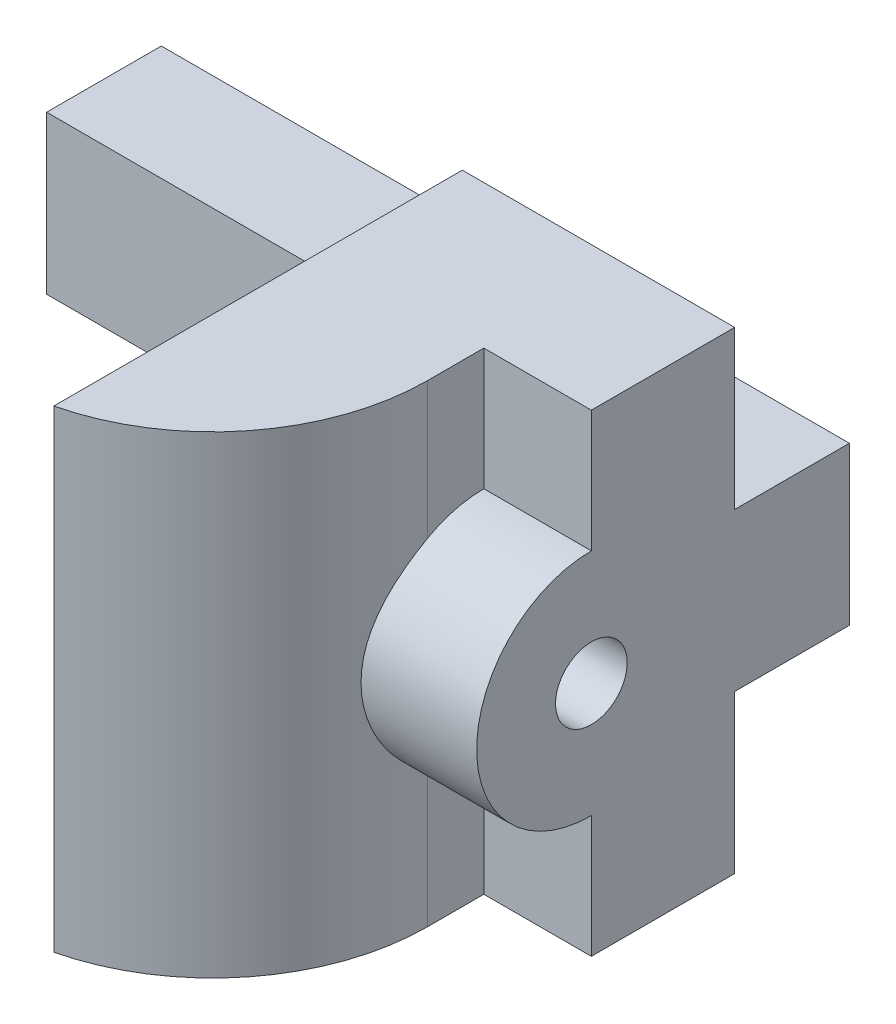
SolidWorks part; units mm, degrees
ref_plane "Front Plane" through (0, 0, 0) normal (1, 0, 0) x (0, 1, 0)
ref_plane "Top Plane" through (0, 0, 0) normal (0, 0, 1) x (0, 1, 0)
ref_plane "Right Plane" through (0, 0, 0) normal (0, 1, 0) x (-1, 0, 0)
sketch "Sketch1" plane through (0, 0, 0) normal (1, 0, 0) x (0, 1, 0)
  line L0 (-115.4321, 0) -> (-16, 0) construction
  line L1 (0, 142.0551) -> (0, -132.6241) construction
  line L6 (11, -36) -> (-11, -36)
  line L7 (-11, -36) -> (-11, -20)
  line L8 (-11, -20) -> (-33, -20)
  line L9 (-33, -20) -> (-33, 0)
  line L10 (-33, 0) -> (-16, 0)
  line L11 (11, -36) -> (11, -20)
  line L12 (11, -20) -> (33, -20)
  line L13 (33, -20) -> (33, 0)
  line L14 (-33, 0) -> (33, 0) construction
  line L15 (-11, -20) -> (11, -20)
  line L16 (16, 0) -> (33, 0)
  line L17 (16, 0) -> (115.4321, 0) construction
  arc A0 (16, 0) -> (-16, 0) centre (0, 0) ccw
  circle A1 centre (0, 0) radius 5
  point P9 (0, 0)
  point P10 (0, -36)
  point P17 (0, 0)
  dimension "D5" = 16
  dimension "D6" = 10
  dimension "D1" = 20
  dimension "D2" = 66
  dimension "D3" = 16
  dimension "D4" = 22
  dimension "D7" = 20
extrude "Boss-Extrude1" add sketch "Sketch1" against normal blind 15 contours L16 A0 L10 L9 L8 L15 L12 L13 A1 region at (0, 0, -6.3698)
extrude "Boss-Extrude2" add sketch "Sketch1<3>" against normal blind 96 contours L15 L7 L6 L11 region at (0, 0, -28)
sketch "Sketch1<3>" plane through (0, 0, 0) normal (1, 0, 0) x (0, 1, 0) same geometry as "Sketch1"
sketch "Sketch2" plane through (0, 33, 0) normal (0, 1, 0) x (-1, 0, 0)
  line L0 (15, 37) -> (15, -20)
  line L1 (15, 37) -> (38, 37)
  line L2 (38, 37) -> (38, -20)
  line L3 (96, -20) -> (15, -20) construction
  line L4 (38, -20) -> (15, -20)
  line L5 (15, -20) -> (0, -20) construction
  line L6 (0, -20) -> (0, 0) construction
  dimension "D1" = 38
  dimension "D2" = 57
extrude "Boss-Extrude3" add sketch "Sketch2" against normal blind 66
fillet "Fillet1" radius 30 1 edges at (-15, 0, 37)
extrude "Cut-Extrude1" cut sketch "Sketch1<4>" against normal through all both and the other way through all contours A1
sketch "Sketch1<4>" plane through (0, 0, 0) normal (1, 0, 0) x (0, 1, 0) same geometry as "Sketch1"
